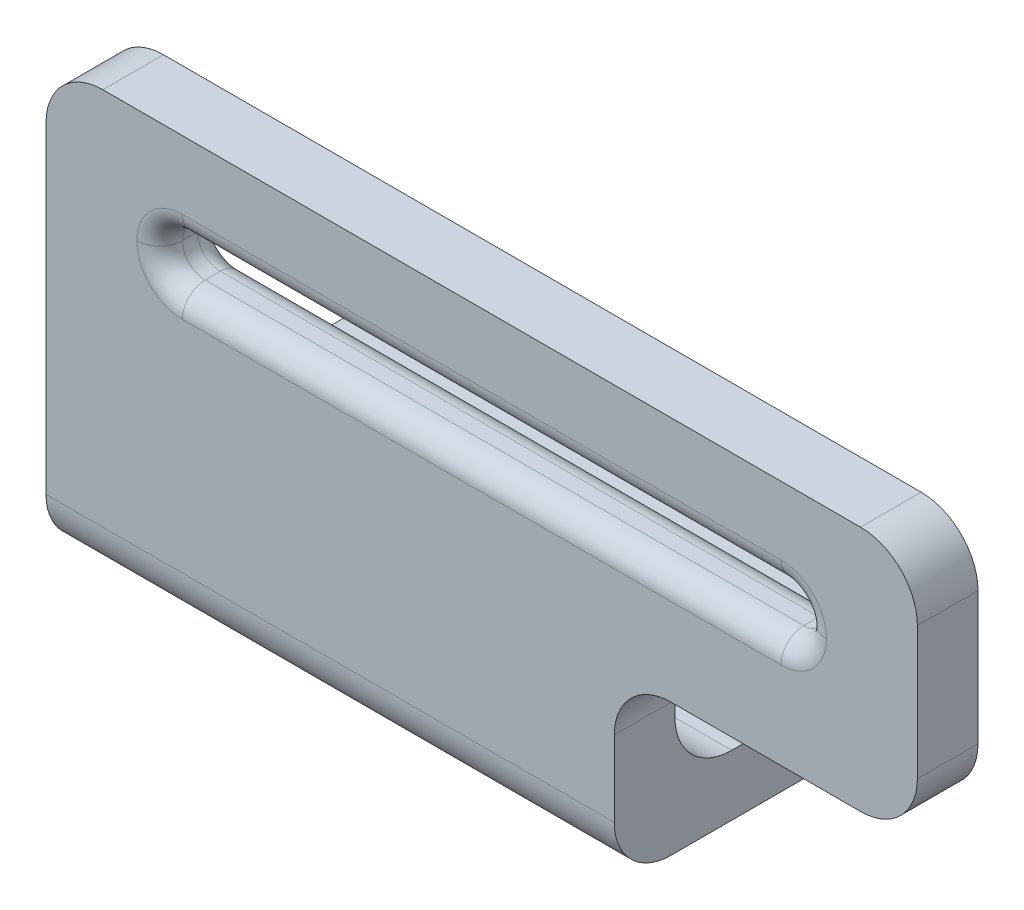
SolidWorks part; units mm, degrees
ref_plane "Front Plane" through (0, 0, 0) normal (0, 0, 1) x (1, 0, 0)
ref_plane "Top Plane" through (0, 0, 0) normal (0, 1, 0) x (1, 0, 0)
ref_plane "Right Plane" through (0, 0, 0) normal (1, 0, 0) x (0, 0, -1)
sketch "Sketch1" plane through (0, 0, 0) normal (1, 0, 0) x (0, 0, -1)
  line L0 (0, 11.5) -> (0, 0)
  line L1 (0, 0) -> (10, 0)
  line L2 (10, 0) -> (10, 1.6)
  line L3 (10, 1.6) -> (1.6, 1.6)
  line L4 (1.6, 1.6) -> (1.6, 11.5)
  line L5 (1.6, 11.5) -> (0, 11.5)
  dimension "D1" = 1.6
  dimension "D2" = 10
  dimension "D3" = 11.5
extrude "Boss-Extrude1" add sketch "Sketch1" along normal blind 23
sketch "Sketch2" plane through (0, 0, 0) normal (0, 0, 1) x (1, 0, 0)
  line L0 (23, 11.5) -> (23, 0) construction
  line L1 (15, 5) -> (23, 5)
  line L2 (15, 5) -> (15, 0)
  line L3 (15, 0) -> (23, 0)
  line L4 (23, 5) -> (23, 0)
  line L5 (20, 9.1) -> (3, 9.1)
  line L6 (20, 9.1) -> (20, 7.9)
  line L7 (20, 7.9) -> (3, 7.9)
  line L8 (3, 9.1) -> (3, 7.9)
  line L9 (3, 8.5) -> (20, 8.5) construction
  line L10 (23, 0) -> (0, 0) construction
  dimension "D1" = 8
  dimension "D2" = 3
  dimension "5" = 5
  dimension "D3" = 1.2
  dimension "D4" = 17
  dimension "D5" = 8.5
extrude "Cut-Extrude1" cut sketch "Sketch2" against normal through all
fillet "Fillet1" radius 0.6 8 edges at (11.5, 9.1, -1.6) (11.5, 7.9, -1.6) (11.5, 7.9, 0) (11.5, 9.1, 0) (20, 9.1, -0.8) (20, 7.9, -0.8) (3, 7.9, -0.8) (3, 9.1, -0.8)
fillet "Fillet2" radius 1.5 8 edges at (7.5, 1.6, -1.6) (7.5, 0, 0) (0, 0.8, -10) (15, 0.8, -10) (0, 11.5, -0.8) (23, 11.5, -0.8) (23, 5, -0.8) (15, 5, -0.8)
